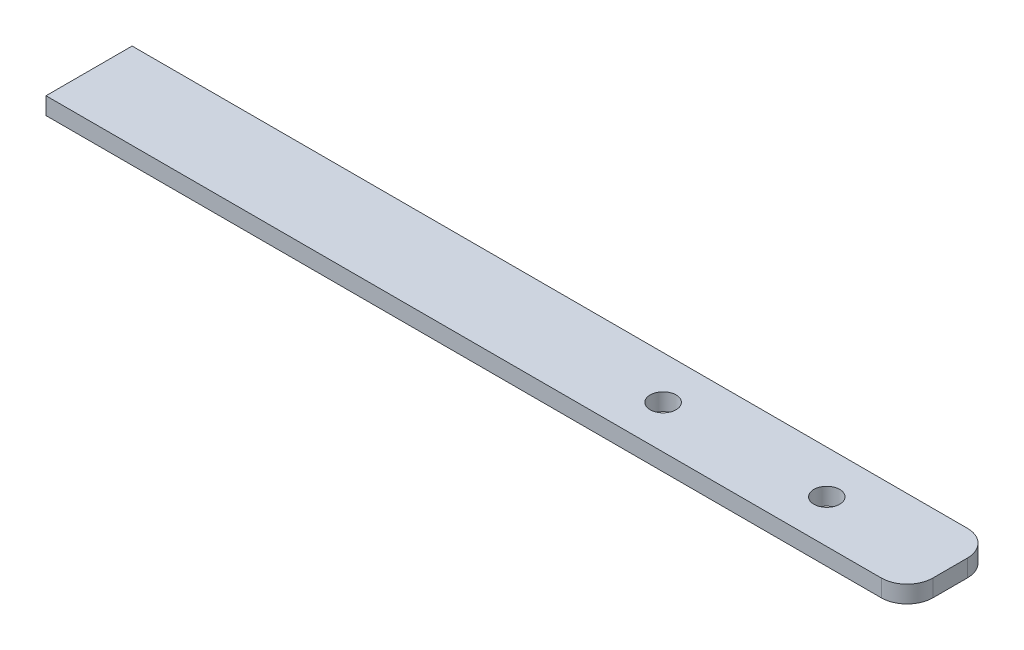
SolidWorks part; units mm, degrees
ref_plane "Front Plane" through (0, 0, 0) normal (0, 0, 1) x (1, 0, 0)
ref_plane "Top Plane" through (0, 0, 0) normal (0, 1, 0) x (1, 0, 0)
ref_plane "Right Plane" through (0, 0, 0) normal (1, 0, 0) x (0, 0, -1)
sketch "Sketch1" plane through (0, 0, 0) normal (0, 1, 0) x (1, 0, 0)
  line L1 (-50, 5) -> (50, 5)
  line L2 (-50, 5) -> (-50, -5)
  line L3 (-50, -5) -> (50, -5)
  line L4 (50, 5) -> (50, -5)
  line L5 (-50, 5) -> (50, -5) construction
  line L6 (-50, -5) -> (50, 5) construction
  point P0 (0, 0)
  dimension "D1" = 10
  dimension "D2" = 100
extrude "Boss-Extrude1" add sketch "Sketch1" along normal blind 2
sketch "Sketch2" plane through (0, 2, 0) normal (0, 1, 0) x (1, 0, 0)
  line L0 (26.3156, 5) -> (26.3156, -5) construction
  line L1 (-50, -5) -> (50, -5) construction
  point P0 (0, 0)
  point P10 (26.3156, 0)
fillet "Fillet1" radius 3 2 edges at (50, 1, 5) (50, 1, -5)
hole_wizard "Ø3.0mm Dowel Hole1" positions "Sketch3" profile "Sketch5" hole size "Ø3.0" standard "ISO" end condition through all
sketch "Sketch3" plane through (0, 2, 0) normal (0, 1, 0) x (1, 0, 0)
  point P0 (35.6745, 0)
  point P5 (16.6695, 0)
  point P8 (0, 0)
  point P9 (35.6745, 0)
  dimension "D1" = 19.005
sketch "Sketch5" plane through (35.6745, 2, 0) normal (1, 0, 0) x (0, 0, 1)
  line L0 (0, 0) -> (0, 2)
  line L1 (0, 2) -> (1.5, 2)
  line L2 (1.5, 2) -> (1.5, 0)
  line L5 (1.5, 0) -> (0, 0)
  line L11 (0, -22.0399) -> (0, 107.95) construction
  point P3 (0, 0)
  point P4 (0, -22.0399)
  dimension "Thru Hole Dia." = 3
  dimension "Thru Hole Depth" = 2
